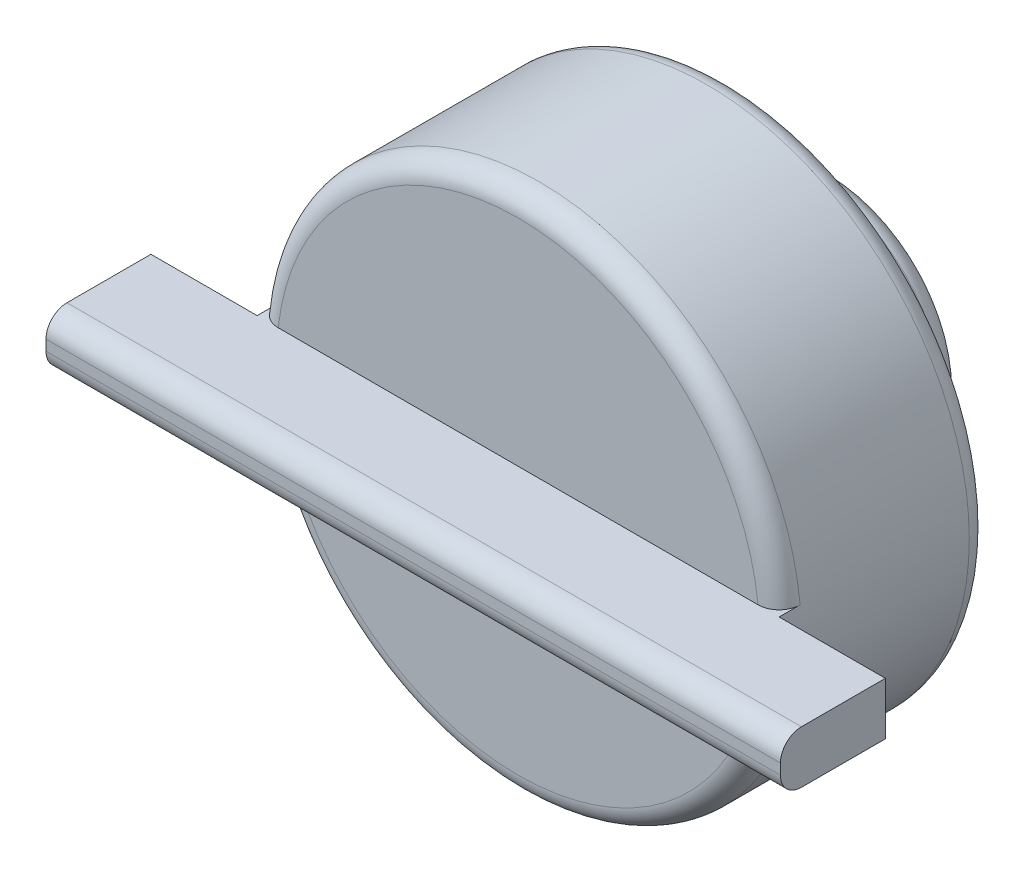
SolidWorks part; units mm, degrees
ref_plane "Alzado" through (0, 0, 0) normal (0, 0, 1) x (1, 0, 0)
ref_plane "Planta" through (0, 0, 0) normal (0, 1, 0) x (1, 0, 0)
ref_plane "Vista lateral" through (0, 0, 0) normal (1, 0, 0) x (0, 0, -1)
sketch "Croquis1" plane through (0, 0, 0) normal (0, 0, 1) x (1, 0, 0)
  circle A0 centre (0, 0) radius 12.5
  circle A1 centre (0, 0) radius 6.5
  dimension "D1" = 13
  dimension "D2" = 25
extrude "Saliente-Extruir1" add sketch "Croquis1" along normal blind 10
sketch "Croquis2" plane through (0, 0, 10) normal (0, 0, 1) x (1, 0, 0)
  circle A0 centre (0, 0) radius 25
extrude "Saliente-Extruir2" add sketch "Croquis2" along normal blind 20
sketch "Croquis3" plane through (0, 0, 30) normal (0, 0, 1) x (1, 0, 0)
  line L1 (-35, 2.5) -> (35, 2.5)
  line L2 (-35, 2.5) -> (-35, -2.5)
  line L3 (-35, -2.5) -> (35, -2.5)
  line L4 (35, 2.5) -> (35, -2.5)
  line L5 (-35, 2.5) -> (35, -2.5) construction
  line L6 (-35, -2.5) -> (35, 2.5) construction
  point P0 (0, 0)
  dimension "D1" = 70
  dimension "D2" = 5
extrude "Saliente-Extruir3" add sketch "Croquis3" along normal blind 10
fillet "Redondeo1" radius 2 8 edges at (0, -2.5, 40) (0, 2.5, 40) (0, -25, 30) (12.5, 0, 10) (25, 0, 10) (6.5, 0, 10) (12.5, 0, 0) (0, 25, 30)
